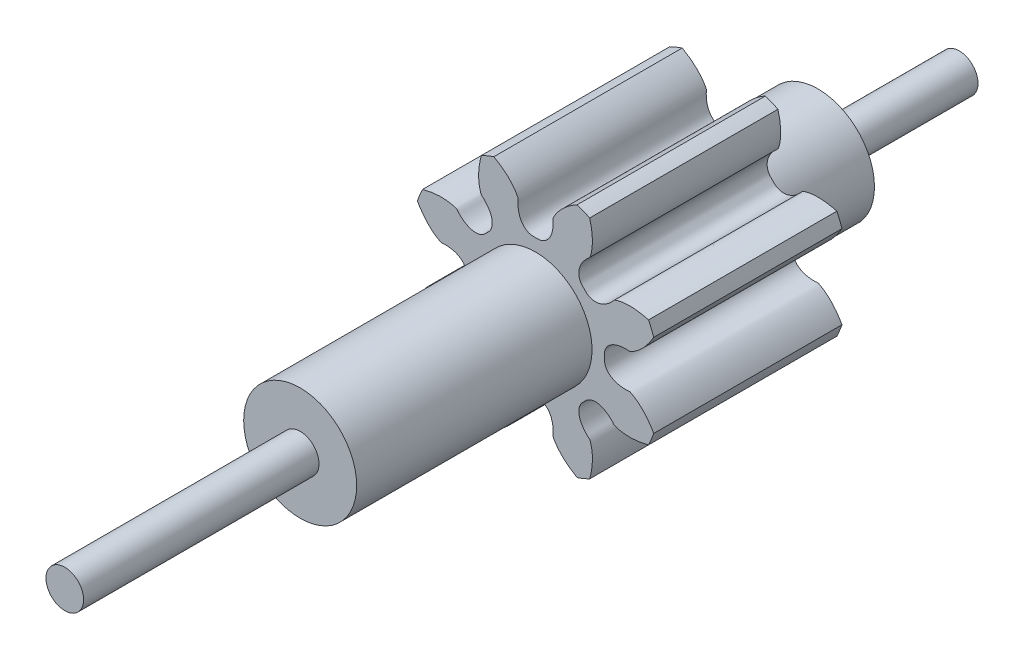
SolidWorks part; units mm, degrees
ref_plane "Alzado" through (0, 0, 0) normal (0, 0, 1) x (1, 0, 0)
ref_plane "Planta" through (0, 0, 0) normal (0, 1, 0) x (1, 0, 0)
ref_plane "Vista lateral" through (0, 0, 0) normal (1, 0, 0) x (0, 0, -1)
ref_axis "Eje1" through (0, 0, 55) along (0, 0, -1)
sketch "SketchRevolveEngranaje 8d" plane through (0, 0, 0) normal (1, 0, 0) x (0, 0, -1)
  line L0 (0, 0) -> (1, 0) construction
  line L1 (-0.75, 0) -> (-0.75, 0.6654)
  line L2 (-0.75, 0.6654) -> (0.25, 0.6654)
  line L3 (0.25, 0.6654) -> (0.25, 0)
  line L4 (0.25, 0) -> (-0.75, 0)
  dimension "D1" = 1
revolve "Engranaje 8d" add sketch "SketchRevolveEngranaje 8d" angle 360 about L0
sketch "SketchToothEngranaje 8d" plane through (0, 0, 0) normal (0, 0, 1) x (1, 0, 0)
  arc A0 (0.6276, 0.221) -> (0.6276, -0.221) centre (0, 0) cw
  spline S0 degree 3 poles (0.6276, -0.221) (0.6216, -0.2104) (0.6123, -0.1952) (0.5988, -0.1764) (0.589, -0.1639) (0.5793, -0.1526) (0.5698, -0.1424) (0.5605, -0.1333) (0.5515, -0.1253) (0.543, -0.1183) (0.5349, -0.1122) (0.5273, -0.1071) (0.5204, -0.1028) (0.5141, -0.0992) (0.5071, -0.0959) (0.4986, -0.0908) (0.4888, -0.0935) (0.4806, -0.0935) (0.4744, -0.0935) (0.4683, -0.0933) (0.4623, -0.0929) (0.4565, -0.0923) (0.4507, -0.0915) (0.4451, -0.0905) (0.4396, -0.0893) (0.4343, -0.088) (0.429, -0.0864) (0.4239, -0.0847) (0.419, -0.0828) (0.4141, -0.0807) (0.4095, -0.0783) (0.4049, -0.0758) (0.4005, -0.073) (0.3963, -0.07) (0.3922, -0.0668) (0.3884, -0.0633) (0.3847, -0.0596) (0.3813, -0.0556) (0.3781, -0.0513) (0.3752, -0.0468) (0.3726, -0.042) (0.3703, -0.0369) (0.3685, -0.0316) (0.3671, -0.0261) (0.3662, -0.0204) (0.3658, -0.0154) (0.3657, -0.0085) (0.3661, 0) (0.3657, 0.0085) (0.3658, 0.0154) (0.3662, 0.0204) (0.3671, 0.0261) (0.3685, 0.0316) (0.3703, 0.0369) (0.3726, 0.042) (0.3752, 0.0468) (0.3781, 0.0513) (0.3813, 0.0556) (0.3847, 0.0596) (0.3884, 0.0633) (0.3922, 0.0668) (0.3963, 0.07) (0.4005, 0.073) (0.4049, 0.0758) (0.4095, 0.0783) (0.4141, 0.0807) (0.419, 0.0828) (0.4239, 0.0847) (0.429, 0.0864) (0.4343, 0.088) (0.4396, 0.0893) (0.4451, 0.0905) (0.4507, 0.0915) (0.4565, 0.0923) (0.4623, 0.0929) (0.4683, 0.0933) (0.4744, 0.0935) (0.4806, 0.0935) (0.4888, 0.0935) (0.4986, 0.0908) (0.5071, 0.0959) (0.5141, 0.0992) (0.5204, 0.1028) (0.5273, 0.1071) (0.5349, 0.1122) (0.543, 0.1183) (0.5515, 0.1253) (0.5605, 0.1333) (0.5698, 0.1424) (0.5793, 0.1526) (0.589, 0.1639) (0.5988, 0.1764) (0.6123, 0.1952) (0.6216, 0.2104) (0.6276, 0.221) knots 0 0 0 0 0.049065 0.071661 0.092966 0.11298 0.131702 0.149133 0.165273 0.180122 0.193679 0.205946 0.216921 0.226605 0.234997 0.248333 0.264642 0.27314 0.281482 0.289673 0.297718 0.305624 0.313396 0.32104 0.328566 0.335981 0.343294 0.350515 0.357655 0.364727 0.371743 0.378718 0.385666 0.392605 0.39955 0.406519 0.41353 0.4206 0.427743 0.434972 0.442299 0.449727 0.457257 0.464883 0.472591 0.480363 0.485222 0.5 0.514778 0.519637 0.527409 0.535117 0.542743 0.550273 0.557701 0.565028 0.572257 0.5794 0.58647 0.593481 0.60045 0.607395 0.614334 0.621282 0.628257 0.635273 0.642345 0.649485 0.656706 0.664019 0.671434 0.67896 0.686604 0.694376 0.702282 0.710327 0.718518 0.72686 0.735358 0.751667 0.765003 0.773395 0.783079 0.794054 0.806321 0.819878 0.834727 0.850867 0.868298 0.88702 0.907034 0.928339 0.950935 1 1 1 1
extrude "ToothExtrudeCutEngranaje 8d" cut sketch "SketchToothEngranaje 8d" against normal blind 0.75 and the other way blind 0.75
pattern_circular "PatternEngranaje 8d" count 8 every 45 about axis through (0, 0, 55) along (0, 0, -1) of "ToothExtrudeCutEngranaje 8d"
sketch "AuxiliarySketchEngranaje 8d" plane through (0, 0, 0) normal (0, 0, 1) x (1, 0, 0)
  circle A0 centre (0, 0) radius 0.5323 construction
  circle A1 centre (0, 0) radius 0.5002 construction
  circle A2 centre (0, 0) radius 0.5495 construction
  circle A3 centre (0, 0) radius 0.6654 construction
  circle A4 centre (0, 0) radius 0.366 construction
  dimension "PitchDiameter" = 1.0646
  dimension "BaseDiameter" = 1.0004
  dimension "FormDiameter" = 1.099
  dimension "MajorDiameter" = 1.3308
  dimension "MinorDiameter" = 0.7319
sketch "Croquis5" plane through (0, 0, 0.75) normal (0, 0, 1) x (1, 0, 0)
  circle A0 centre (0, 0) radius 0.3
  dimension "D1" = 0.6
extrude "Saliente-Extruir1" add sketch "Croquis5" along normal blind 1.25
sketch "Croquis6" plane through (0, 0, 2) normal (0, 0, 1) x (1, 0, 0)
  circle A0 centre (0, 0) radius 0.1
  dimension "D1" = 0.2
extrude "Saliente-Extruir2" add sketch "Croquis6" along normal blind 1.25
sketch "Croquis7" plane through (0, 0, -0.25) normal (0, 0, -1) x (-1, 0, 0)
  circle A0 centre (0, 0) radius 0.3
  dimension "D1" = 0.6
extrude "Saliente-Extruir3" add sketch "Croquis7" along normal blind 0.5
sketch "Croquis8" plane through (0, 0, -0.75) normal (0, 0, -1) x (-1, 0, 0)
  circle A0 centre (0, 0) radius 0.1
  dimension "D1" = 0.2
extrude "Saliente-Extruir4" add sketch "Croquis8" along normal blind 0.75
